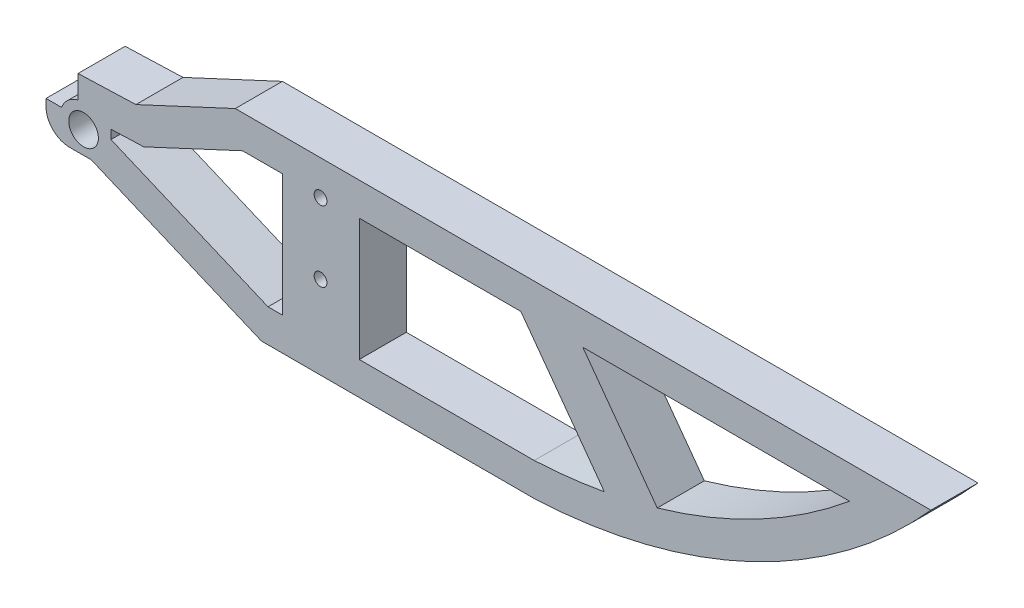
SolidWorks part; units mm, degrees
ref_plane "Front Plane" through (0, 0, 0) normal (0, 0, 1) x (1, 0, 0)
ref_plane "Top Plane" through (0, 0, 0) normal (0, 1, 0) x (1, 0, 0)
ref_plane "Right Plane" through (0, 0, 0) normal (1, 0, 0) x (0, 0, -1)
sketch "Sketch1" plane through (0, 0, 0) normal (0, 0, 1) x (1, 0, 0)
  line L1 (120.65, 25.4) -> (-120.65, 25.4)
  line L2 (120.65, 25.4) -> (120.65, -25.4)
  line L3 (120.65, -25.4) -> (-120.65, -25.4)
  line L4 (-120.65, 25.4) -> (-120.65, -25.4)
  line L5 (120.65, 25.4) -> (-120.65, -25.4) construction
  line L6 (120.65, -25.4) -> (-120.65, 25.4) construction
  point P0 (0, 0)
  dimension "D1" = 241.3
  dimension "D2" = 50.8
extrude "Boss-Extrude1" add sketch "Sketch1" along normal blind 12.7
sketch "Sketch3" plane through (0, 0, 12.7) normal (0, 0, 1) x (1, 0, 0)
  line L0 (0, 0) -> (-120.65, 0) construction
  line L1 (-120.65, 25.4) -> (-120.65, -25.4) construction
  circle A0 centre (-107.95, 0) radius 4
  dimension "D2" = 8
  dimension "D1" = 12.7
extrude "Cut-Extrude1" cut sketch "Sketch3" against normal through all
sketch "Sketch5" plane through (0, 0, 12.7) normal (0, 0, 1) x (1, 0, 0)
  line L0 (-120.65, -25.4) -> (120.65, -25.4) construction
  line L1 (-105.8942, -6.008) -> (-59.9903, -25.4)
  line L2 (-107.95, 6.35) -> (-67.0151, 25.4)
  line L3 (120.65, 25.4) -> (-120.65, 25.4) construction
  line L4 (-67.0151, 25.4) -> (-120.65, 25.4)
  line L5 (-120.65, 25.4) -> (-120.65, -25.4)
  line L6 (-120.65, -25.4) -> (-59.9903, -25.4)
  line L7 (120.65, 25.4) -> (120.65, -25.4)
  line L8 (120.65, -25.4) -> (0, -25.4)
  line L9 (-109.9582, -6.0241) -> (-105.8942, -6.008)
  line L10 (-118.0862, -6.0241) -> (-109.9582, -6.0241)
  line L11 (-118.0862, -6.0241) -> (-118.0862, 2.2309)
  line L12 (-118.0862, 2.2309) -> (-113.8952, 2.2309)
  arc A0 (0, -25.4) -> (120.65, 25.4) centre (6.9175, 126.8429) ccw
  arc A1 (-109.9582, -6.0241) -> (-105.8942, -6.008) centre (-107.95, 0) ccw construction
  arc A2 (-107.95, 6.35) -> (-113.8952, 2.2309) centre (-107.95, 0) ccw
  point P15 (-116.1445, -2.9908)
  line M3 (-120.65, 25.4) -> (-120.65, -25.4)
  line M4 (-120.65, -25.4) -> (120.65, -25.4)
  line M5 (120.65, -25.4) -> (120.65, 25.4)
  line M6 (120.65, 25.4) -> (-120.65, 25.4)
  dimension "D1" = 152.4
  dimension "D2" = 12.7
  dimension "D3" = 45.1505
  dimension "D4" = 45.9039
  dimension "D5" = 8.255
  dimension "D6" = 4.191
  dimension "D7" = 8.128
extrude "Cut-Extrude2" cut sketch "Sketch5" against normal through all contours A2 L2 L1 M6 M3 M4 | A0 L8 M5 region at (-83.2502, -16.4329, 12.7) region at (93.5193, -10.6939, 12.7)
sketch "Sketch6" plane through (0, 0, 12.7) normal (0, 0, 1) x (1, 0, 0)
  line L0 (-107.95, 0) -> (91.396, 0) construction
  arc A0 (13.8349, -25.4) -> (120.65, 25.4) centre (6.9175, 126.8429) ccw construction
  circle A1 centre (19.05, 0) radius 3.1347
  dimension "D1" = 127
sketch "Sketch7" plane through (0, 0, 0) normal (0, 0, -1) x (-1, 0, 0)
  line L0 (44.0204, -2.9977) -> (44.0204, 16.0523) construction
  point P3 (44.0204, -2.9977)
  point P4 (44.0204, 16.0523)
  dimension "D1" = 19.05
sketch "Sketch8" plane through (0, 0, 0) normal (0, 0, -1) x (-1, 0, 0)
  point P0 (44.0204, 16.0523)
  point P3 (44.0204, -2.9977)
hole_wizard "Tap Drill for #8-32 Tap1" positions "Sketch8" profile "Sketch9" hole size "#8-32" standard "ANSI Inch" end condition through all
sketch "Sketch9" plane through (-44.0204, 16.0523, 0) normal (1, 0, 0) x (0, 1, 0)
  line L0 (0, 0) -> (0, 12.7)
  line L1 (0, 12.7) -> (1.7272, 12.7)
  line L2 (1.7272, 12.7) -> (1.7272, 0)
  line L5 (1.7272, 0) -> (0, 0)
  line L11 (0, -6.35) -> (0, 107.95) construction
  dimension "Thru Hole Dia." = 3.4544
  dimension "Thru Hole Depth" = 12.7
ref_plane "Plane1" through (-114.3, 0, 0) normal (-1, 0, 0) x (0, 0, 1)
sketch "Sketch10" plane through (-114.3, 0, 0) normal (-1, 0, 0) x (0, 0, 1)
  line L0 (0, 0) -> (12.7, 0) construction
  line L1 (12.7, -3.1347) -> (12.7, 3.1347) construction
  circle A0 centre (6.0894, 0) radius 1.905
  dimension "D1" = 3.81
extrude "Cut-Extrude3" cut sketch "Sketch10" against normal blind 5.08
sketch "Sketch11" plane through (0, 0, 12.7) normal (0, 0, 1) x (1, 0, 0)
  line L0 (-93.8249, 12.9234) -> (-109.4459, 12.9234) construction
  line L1 (-107.95, 6.35) -> (-67.0151, 25.4) construction
  line L2 (-109.4459, 12.9234) -> (-109.4459, 5.6538) construction
  line L3 (-93.8249, 12.9234) -> (-109.4459, 5.6538)
  line L4 (-93.8249, 12.9234) -> (-109.4459, 12.3779)
  line L5 (-109.4459, 12.3779) -> (-109.4459, 5.6538)
  circle A1 centre (-107.95, 0) radius 4 construction
  dimension "D1" = 15.621
  dimension "D2" = 5.6538
  dimension "D3" = 178
extrude "Boss-Extrude2" add sketch "Sketch11" against normal up to surface (12.7 mm away) up to face at (-45.7476, 16.0523, 0)
sketch "Sketch12" plane through (0, 0, 12.7) normal (0, 0, 1) x (1, 0, 0)
  line L1 (10.0217, 16.51) -> (-33.5733, 16.51)
  line L24 (-33.5733, 16.51) -> (-33.5733, -16.51)
  line L25 (-54.2244, 16.51) -> (-54.2244, -16.51)
  line L26 (-54.2244, 16.51) -> (-65.0478, 16.51)
  line L27 (-33.5733, -16.51) -> (13.63, -16.51)
  line L28 (10.0217, 16.51) -> (32.5572, -14.3581)
  line L29 (26.7339, 16.51) -> (46.8231, -11.0072)
  line L30 (-100.5559, 3.793) -> (-100.5559, 1.3876)
  line L31 (-100.5559, 1.3876) -> (-58.1896, -16.51)
  line L32 (-58.1896, -16.51) -> (13.63, -16.51)
  line L33 (98.6876, 16.51) -> (-65.0478, 16.51)
  line L34 (-65.0478, 16.51) -> (-91.7106, 4.1018)
  line L35 (-91.7106, 4.1018) -> (-100.5559, 3.793)
  line L36 (-100.5559, 3.793) -> (-100.5559, 1.3876)
  line L37 (-100.5559, 1.3876) -> (-58.1896, -16.51)
  line L38 (-58.1896, -16.51) -> (-54.2244, -16.51)
  line L39 (98.6876, 16.51) -> (26.7339, 16.51)
  line L40 (-65.0478, 16.51) -> (-91.7106, 4.1018)
  line L41 (-91.7106, 4.1018) -> (-100.5559, 3.793)
  arc A0 (46.8231, -11.0072) -> (98.6876, 16.51) centre (6.9175, 126.8429) ccw
  arc A10 (13.63, -16.51) -> (98.6876, 16.51) centre (6.9175, 126.8429) ccw
  arc A11 (13.63, -16.51) -> (32.5572, -14.3581) centre (6.9175, 126.8429) ccw
  dimension "D1" = 8.89
extrude "Cut-Extrude4" cut sketch "Sketch12" against normal through all
sketch "Sketch13" plane through (0, 0, 12.7) normal (0, 0, 1) x (1, 0, 0)
  line L0 (-79.3724, -17.2121) -> (-87.4623, -19.4143)
  line L1 (-105.8942, -6.008) -> (-59.9903, -25.4) construction
  line L2 (-87.4623, -19.4143) -> (-89.1909, -13.0643)
  line L4 (-79.3724, -17.2121) -> (-89.1909, -13.0643)
  circle A0 centre (-107.95, 0) radius 4 construction
  dimension "D1" = 90
  dimension "D2" = 6.35
  dimension "D3" = 22.86
fillet "Fillet1" radius 6.35 1 edges at (-118.0862, -6.0241, 6.35)
sketch "Sketch14" plane through (0.0221, -5.5891, 0) normal (0.004, -1, 0) x (1, 0.004, 0)
  line L0 (-109.9812, 0) -> (-109.9812, 12.7) construction
  line L2 (-109.9812, 6.35) -> (-105.9171, 6.35) construction
  line L3 (-105.9171, 0) -> (-105.9171, 12.7) construction
  line L4 (-107.9492, 0) -> (-107.9492, 12.7) construction
  line L5 (-109.9812, 0) -> (-105.9171, 0) construction
  line L6 (-109.9812, 12.7) -> (-105.9171, 12.7) construction
  circle A0 centre (-107.9492, 6.35) radius 1.27
  point P15 (-107.2722, 4.9738)
  point P16 (-107.9492, 6.35)
  dimension "D1" = 2.54
extrude "Cut-Extrude5" cut sketch "Sketch14" against normal blind 6.35
